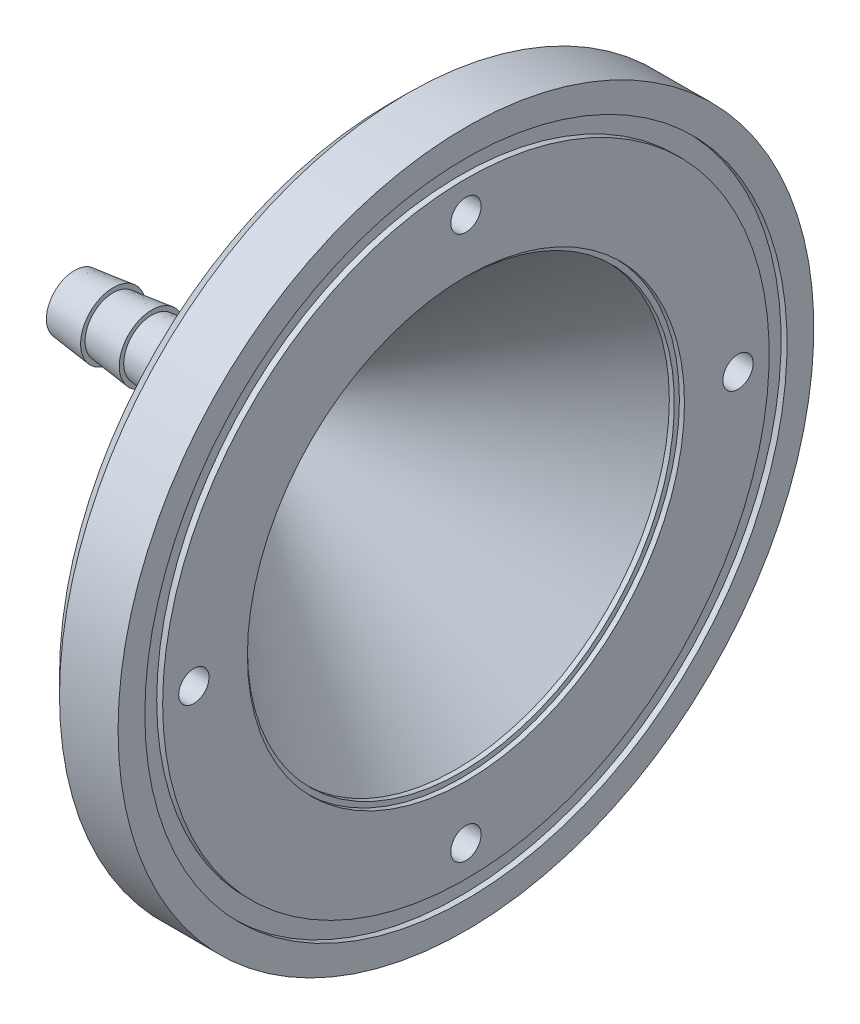
SolidWorks part; units mm, degrees
ref_plane "Front Plane" through (0, 0, 0) normal (0, 0, 1) x (1, 0, 0)
ref_plane "Top Plane" through (0, 0, 0) normal (0, 1, 0) x (1, 0, 0)
ref_plane "Right Plane" through (0, 0, 0) normal (1, 0, 0) x (0, 0, -1)
sketch "Sketch1" plane through (0, 0, 0) normal (0, 0, 1) x (1, 0, 0)
  line L0 (-801.9206, 0) -> (36107.5283, 0) construction
  line L3 (-14.1752, 3.65) -> (-14.1752, 3.15)
  line L8 (-18.5085, 1.9) -> (0, 1.9)
  line L9 (-18.5085, 1.9) -> (-18.5085, 3.15)
  line L10 (25.3752, 24.5) -> (25.3752, 39)
  line L12 (25.3752, 39) -> (16.8092, 39)
  line L16 (25.3752, 24.5) -> (24.8092, 24.5)
  line L17 (24.8092, 24.5) -> (24.8092, 23.934)
  line L18 (16.8092, 39) -> (16.8092, 23.934)
  line L20 (0, 1.9) -> (24.2432, 23.934)
  line L21 (-18.5085, 3.15) -> (-14.1752, 3.65)
  line L22 (24.2432, 23.934) -> (24.8092, 23.934)
  line L23 (-14.1752, 3.15) -> (-9.8419, 3.65)
  line L25 (-9.8419, 3.15) -> (-5.5085, 3.65)
  line L26 (-9.8419, 3.65) -> (-9.8419, 3.15)
  line L27 (-5.5085, 3.65) -> (16.8092, 23.934)
  line L29 (24.7082, 36) -> (24.7082, 34)
  line L30 (24.7082, 34) -> (25.3752, 34)
  line L32 (24.7082, 36) -> (25.3752, 36)
  dimension "D3" = 0.566
  dimension "D2" = 7.3
  dimension "D6" = 3.8
  dimension "D7" = 6.3
  dimension "D5" = 39
  dimension "D8" = 24.5
  dimension "D10" = 0.566
  dimension "D4" = 5
  dimension "D9" = 0.566
  dimension "D11" = 13
  dimension "D12" = 8.566
  dimension "D14" = 2
  dimension "D13" = 36
  dimension "D15" = 0.667
revolve "Revolve17" add sketch "Sketch1" angle 360 about L0 region at (-14.7499, 3.4, 0)
sketch "Sketch4" plane through (16.8092, 0, 0) normal (-1, 0, 0) x (0, 0, 1)
  line L0 (0, 23.934) -> (0, 39) construction
  circle A0 centre (0, 0) radius 30.5 construction
  circle A1 centre (0, 0) radius 23.934 construction
  circle A2 centre (0, 0) radius 39 construction
  point P3 (0, 30.5)
  point P7 (30.5, 0)
  point P12 (-30.5, 0)
  point P13 (0, -30.5)
  point P26 (0, 0)
  dimension "D1" = 8.5
  dimension "D2" = 8.5
hole_wizard "CBORE for M3 Hex Socket Head Cap Screw2" positions "Sketch4" profile "Sketch5" counterbore size "M3" standard "ISO"
sketch "Sketch5" plane through (16.8092, -30.5, 0) normal (0, 1, 0) x (0, 0, 1)
  line L0 (0, 0) -> (0, 9.5875)
  line L1 (0, 9.5875) -> (1.7, 8.566)
  line L2 (1.7, 8.566) -> (1.7, 3.4)
  line L3 (1.7, 3.4) -> (3.25, 3.4)
  line L4 (3.25, 3.4) -> (3.25, 0)
  line L5 (3.25, 0) -> (0, 0)
  line L10 (0, 9.5875) -> (-1.7, 8.566) construction
  line L11 (0, -6.35) -> (0, 107.95) construction
  dimension "Hole Dia." = 3.4
  dimension "Hole Depth" = 8.566
  dimension "C'Bore Dia." = 6.5
  dimension "C'Bore Depth" = 3.4
  dimension "Drill Angle" = 118
chamfer "Chamfer1" distance 2 angle 45 1 edges at (16.8092, 0, 39)
sketch "Sketch6" plane through (25.3752, 0, 0) normal (1, 0, 0) x (0, 0, -1)
  line L0 (0, 39) -> (0, 24.5)
  circle A0 centre (0, 0) radius 39
  circle A1 centre (0, 0) radius 39 construction
  circle A2 centre (0, 0) radius 24.5 construction
equation "\"D10@Sketch1\"=\"D3@Sketch1\""
equation "\"D9@Sketch1\"=\"D3@Sketch1\""
